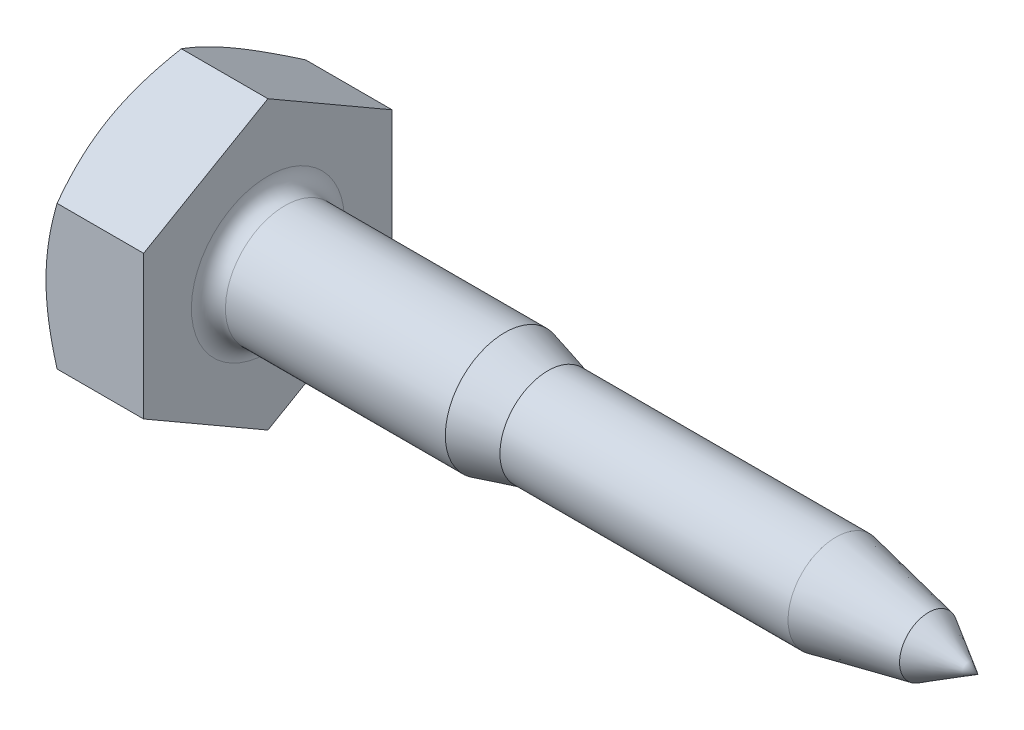
SolidWorks part; units mm, degrees
ref_plane "Front Plane" through (0, 0, 0) normal (0, 0, 1) x (1, 0, 0)
ref_plane "Top Plane" through (0, 0, 0) normal (0, 1, 0) x (1, 0, 0)
ref_plane "Right Plane" through (0, 0, 0) normal (1, 0, 0) x (0, 0, -1)
sketch "Sketch1" plane through (0, 0, 0) normal (0, 0, 1) x (1, 0, 0)
  line L0 (-15.875, 0) -> (15.875, 0) construction
  line L1 (-20.2406, 0) -> (-20.2406, 5.5562)
  line L2 (-20.2406, 5.5562) -> (-15.875, 5.5562)
  line L3 (-15.875, 5.5562) -> (-15.875, 2.6591)
  line L4 (-5.2832, 3.175) -> (15.875, 3.175)
  line L5 (15.875, 0) -> (15.875, 3.175)
  line L6 (15.875, 0.1588) -> (9.525, 2.1431) construction
  line L7 (-5.2832, 0) -> (-5.2832, 3.175) construction
  line L8 (-15.875, 2.6591) -> (-5.2832, 2.6591)
  line L9 (15.875, 2.1431) -> (15.875, 3.175) construction
  line L10 (15.875, 2.6591) -> (-20.2406, 2.6591) construction
  line L11 (9.525, 3.175) -> (9.525, -3.175) construction
  line L12 (-10.5791, 2.6591) -> (-10.5791, 0) construction
  line L13 (-14.8158, 0) -> (-6.3424, 0) construction
  line L14 (-14.8158, 0) -> (-14.8158, 2.6591) construction
  line L15 (-6.3424, 0) -> (-6.3424, 2.6591) construction
  point P2 (-5.2832, 0)
  point P8 (15.875, 2.1431)
  point P9 (15.875, -3.175)
  point P16 (3.175, -3.175)
  point P27 (-10.5791, 0)
  dimension "Length" = 31.75
  dimension "Min Thread Lg." = 21.1582
  dimension "Screw Size" = 6.35
  dimension "D2" = 6.35
  dimension "D4" = 17.354
  dimension "D3" = 14.8082
  dimension "D5" = 0.3175
  dimension "D6" = 3.175
  dimension "D7" = 1.0319
  dimension "D1" = 6.35
  dimension "Hex" = 11.1125
  dimension "D8" = 4.2862
  dimension "Head Height" = 4.3656
  dimension "D9" = 10.5918
  dimension "D10" = 8.4734
ref_plane "Plane1" through (9.525, 0, 0) normal (1, 0, 0) x (0, 0, -1)
sketch "Sketch2" plane through (9.525, 0, 0) normal (1, 0, 0) x (0, 0, -1)
  circle A0 centre (0, 0) radius 3.175
curve "Helix/Spiral1" pitch 2.54 height 17.3482 turns 6.83 parameters "Pitch"=2.54
sketch "Sketch4" plane through (9.525, 0, 0) normal (1, 0, 0) x (0, 0, -1)
  circle A1 centre (0, 0) radius 3.175
  circle A2 centre (0, 0) radius 3.175
  dimension "D1" = 0
curve "Helix/Spiral2"
sketch "Sketch6" plane through (0, 0, 0) normal (0, 0, 1) x (1, 0, 0)
  line L0 (-20.2406, 0) -> (-20.2406, 5.5562) construction
  line L1 (-20.2406, 5.5562) -> (-15.875, 5.5562) construction
  line L2 (-15.875, 5.5562) -> (-15.875, 2.6591) construction
  line L3 (9.525, 2.1431) -> (-3.3577, 2.1431)
  line L4 (-3.3577, 2.1431) -> (-5.2832, 2.6591)
  line L5 (-20.2406, 0) -> (-20.2406, 5.5562)
  line L6 (-20.2406, 5.5562) -> (-15.875, 5.5562)
  line L7 (-15.875, 5.5562) -> (-15.875, 2.6591)
  line L8 (-15.875, 2.6591) -> (-5.2832, 2.6591) construction
  line L9 (-20.2406, 0) -> (15.875, 0)
  line L10 (-5.2832, 2.6591) -> (-15.875, 2.6591)
  line L11 (-5.2832, 0) -> (-5.2832, 3.175) construction
  line L12 (-20.2406, 0) -> (19.9939, 0) construction
  line L13 (15.875, 0) -> (13.6634, 1.2959)
  line L15 (9.525, 2.1431) -> (13.6634, 1.2959)
  dimension "D1" = 11.569
  dimension "D2" = 15
  dimension "D3" = 30.37
revolve "Revolve1" add sketch "Sketch6" angle 360 about L12
sketch "Sketch15" plane through (0, 0, 0) normal (1, 0, 0) x (0, 0, -1)
  line L1 (0, 6.4158) -> (-5.5563, 3.2079)
  line L2 (-5.5563, 3.2079) -> (-5.5562, -3.2079)
  line L3 (-5.5562, -3.2079) -> (0, -6.4158)
  line L4 (0, -6.4158) -> (5.5563, -3.2079)
  line L5 (5.5563, -3.2079) -> (5.5563, 3.2079)
  line L6 (5.5563, 3.2079) -> (0, 6.4158)
  circle A0 centre (0, 0) radius 5.5562 construction
extrude "Boss-Extrude2" add sketch "Sketch15" along normal up to vertex (-15.875 mm away) from vertex up to point (-15.875, 2.6591, 0) starting at point (-20.2406, 5.5562, 0)
sketch "Sketch16" plane through (-20.2406, 0, 0) normal (-1, 0, 0) x (0, 0, 1)
  circle A0 centre (0, 0) radius 5.5562 construction
  circle A1 centre (0, 0) radius 5.5562
extrude "Cut-Extrude7" cut sketch "Sketch16" against normal through all draft 60 flip side to cut
fillet "Fillet1" radius 0.762 1 edges at (-15.875, -2.6591, 0)
ref_axis "Center Axis 1" through (-33.622, 0, 0) along (1, 0, 0)
ref_plane "Contact Plane 1" through (-15.875, 0, 0) normal (1, 0, 0) x (0, 0, -1)
sketch "Sketch3" [suppressed] plane through (0, 0, 0) normal (0, 0, 1) x (1, 0, 0)
  line L0 (9.6044, 3.175) -> (10.2001, 2.1431) construction
  line L1 (9.6044, 3.175) -> (9.4456, 3.175)
  line L2 (9.4456, 3.175) -> (8.8499, 2.1431) construction
  line L3 (8.8499, 2.1431) -> (10.2001, 2.1431) construction
  line L4 (9.6044, 3.175) -> (9.525, 3.175) construction
  line L5 (9.525, 3.175) -> (9.525, 2.1431) construction
  line L6 (-5.2832, 3.175) -> (15.875, 3.175) construction
  line L7 (9.6044, 3.175) -> (10.7315, 1.2228)
  line L8 (10.7315, 1.2228) -> (8.3185, 1.2228)
  line L9 (8.3185, 1.2228) -> (9.4456, 3.175)
  line L15 (15.875, 2.1431) -> (15.875, 3.175) construction
  line L16 (15.875, 2.6591) -> (46.99, 2.6591) construction
  dimension "D1" = 60
  dimension "D2" = 0.1588
  dimension "D3" = 2.413
sweep "Sweep1" [suppressed] add profiles "Sketch3" path "Helix/Spiral1"
sketch "Sketch5" [suppressed] plane through (0, 0, 0) normal (0, 0, 1) x (1, 0, 0)
  line L4 (9.4456, 3.175) -> (8.3185, 1.2228)
  line L5 (9.4456, 3.175) -> (8.3185, 1.2228)
  line L6 (8.3185, 1.2228) -> (10.7315, 1.2228)
  line L7 (9.6044, 3.175) -> (9.4456, 3.175)
  line L8 (8.3185, 1.2228) -> (10.7315, 1.2228)
  line L9 (10.7315, 1.2228) -> (9.6044, 3.175)
  line L10 (10.7315, 1.2228) -> (9.6044, 3.175)
  line L11 (9.6044, 3.175) -> (9.4456, 3.175)
  dimension "D1" = 0
sweep "Sweep2" [suppressed] add profiles "Sketch5" path "Helix/Spiral2"
sketch "Sketch19" [suppressed] plane through (0, 0, 0) normal (0, 0, 1) x (1, 0, 0)
  line L0 (15.875, 0) -> (13.6634, 1.2959) construction
  line L1 (-20.2406, 0) -> (19.9939, 0) construction
  line L2 (14.6685, 0) -> (19.9939, 0)
  line L3 (19.9939, 0) -> (19.9939, 3.175)
  line L4 (12.6246, 3.175) -> (19.9939, 3.175)
  line L5 (-5.2832, 3.175) -> (15.875, 3.175) construction
  line L7 (14.6685, 0) -> (14.6685, 0.707)
  line L8 (14.6685, 0.707) -> (12.6246, 3.175)
  line L9 (-15.875, 0) -> (15.875, 0) construction
  line L10 (15.875, 0) -> (15.875, 3.175) construction
  dimension "D1" = 20
  dimension "D2" = 1.2065
revolve "Cut-Revolve12" [suppressed] cut sketch "Sketch19" angle 360 about L2
sketch "Sketch7" [suppressed] plane through (0, 0, 0) normal (0, 0, 1) x (1, 0, 0)
  line L0 (-15.875, 0) -> (15.875, 0) construction
  line L1 (-20.2406, -5.5562) -> (-5.2832, -5.5563)
  line L2 (-20.2406, -5.5562) -> (-20.2406, 5.5562)
  line L3 (-20.2406, 5.5562) -> (-5.2832, 5.5563)
  line L4 (-5.2832, -5.5563) -> (-5.2832, 5.5563)
  line L5 (-20.2406, -5.5562) -> (-5.2832, 5.5563) construction
  line L6 (-20.2406, 5.5562) -> (-5.2832, -5.5563) construction
  point P0 (-12.7619, 0)
extrude "Cut-Extrude1" [suppressed] cut sketch "Sketch7" against normal through all both and the other way through all
sketch "Sketch12" [suppressed] plane through (0, 0, 0) normal (1, 0, 0) x (0, 0, -1)
  circle A0 centre (0, 0) radius 2.1431
extrude "Cut-Extrude4" [suppressed] cut sketch "Sketch12" along normal through all draft 45 from vertex flip side to cut
combine bodies "Combine2" [suppressed] operation type add bodies to combine 127 141
equation "\"D2@Sketch1\"=\"Screw Size@Sketch1\"*1"
equation "\"D6@Helix/Spiral2\"=\"D4@Sketch1\"*1"
equation "\"D5@Sketch1\"=\"Screw Size@Sketch1\"*.05"
equation "\"D3@Helix/Spiral2\"=\"D2@Sketch1\""
equation "\"D3@Sketch3\"=(\"Pitch@Helix/Spiral1\"/1)*.950"
equation "\"D4@Helix/Spiral2\"=\"Pitch@Helix/Spiral1\""
equation "\"D3@Helix/Spiral1\"=\"D3@Sketch1\"+\"Pitch@Helix/Spiral1\""
equation "\"D1@Sketch6\"=\"D4@Sketch1\"/1.50"
equation "\"D6@Sketch1\"=\"Screw Size@Sketch1\"/2"
equation "\"D2@Sketch3\"=(\"Pitch@Helix/Spiral1\"/2)*.125"
equation "\"D1@Sketch1\"=\"Pitch@Helix/Spiral1\"*2.50"
equation "\"D3@Sketch6\"=\"D4@Sketch1\"*1.75"
equation "\"D2@Sketch19\"=\"D3@Sketch3\"/2"
equation "\"D8@Sketch1\"=\"Screw Size@Sketch1\"*.6750"
equation "\"D10@Sketch1\"=\"D9@Sketch1\"*.8"
